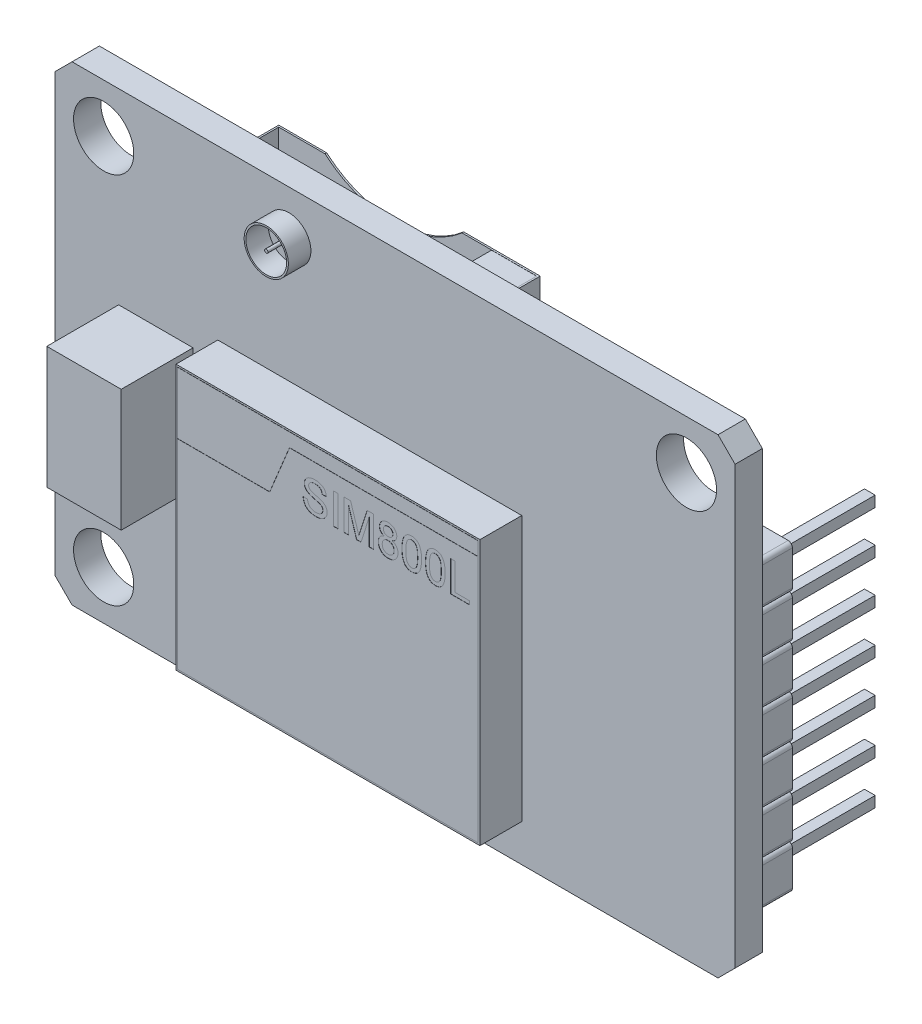
SolidWorks part; units mm, degrees
material "S235 (E24)"
ref_plane "Plan1" through (0, 0, 0) normal (0, 0, 1) x (1, 0, 0)
ref_plane "Plan2" through (0, 0, 0) normal (0, 1, 0) x (1, 0, 0)
ref_plane "Plan3" through (0, 0, 0) normal (1, 0, 0) x (0, 0, -1)
sketch "Esquisse1" plane through (0, 0, 0) normal (0, 0, 1) x (1, 0, 0)
  line L0 (17.075, 10.935) -> (-17.075, 10.935) construction
  line L1 (-19.925, 13.785) -> (19.925, 13.785)
  line L2 (-19.925, 13.785) -> (-19.925, -13.785)
  line L3 (-19.925, -13.785) -> (19.925, -13.785)
  line L4 (19.925, 13.785) -> (19.925, -13.785)
  line L5 (-19.925, 13.785) -> (19.925, -13.785) construction
  line L6 (-19.925, -13.785) -> (19.925, 13.785) construction
  line L7 (-17.075, 10.935) -> (-17.075, -10.935) construction
  line L8 (-17.075, -10.935) -> (17.075, -10.935) construction
  line L9 (17.075, -10.935) -> (17.075, 10.935) construction
  line L10 (0, 0) -> (-17.075, 0) construction
  line L11 (0, 10.935) -> (0, 0) construction
  circle A0 centre (17.075, 10.935) radius 1.765
  circle A1 centre (-17.075, 10.935) radius 1.765
  circle A2 centre (-17.075, -10.935) radius 1.765
  point P0 (0, 0)
  dimension "D3" = 3.53
  dimension "D1" = 39.85
  dimension "D2" = 27.57
  dimension "D4" = 2.85
  dimension "D5" = 2.85
extrude "Boss.-Extru.1" add sketch "Esquisse1" along normal blind 1.6
chamfer "Chanfrein1" distance 1 angle 45 4 edges at (19.925, -13.785, 0.8) (-19.925, -13.785, 0.8) (-19.925, 13.785, 0.8) (19.925, 13.785, 0.8)
sketch "Esquisse2" plane through (0, 0, 1.6) normal (0, 0, 1) x (1, 0, 0)
  line L0 (-18.925, -13.785) -> (18.925, -13.785) construction
  line L1 (-10.385, 3.935) -> (7.425, 3.935)
  line L2 (-10.385, 3.935) -> (-10.385, -11.595)
  line L3 (-10.385, -11.595) -> (7.425, -11.595)
  line L4 (7.425, 3.935) -> (7.425, -11.595)
  line L5 (-10.385, 3.935) -> (7.425, -11.595) construction
  line L6 (-10.385, -11.595) -> (7.425, 3.935) construction
  line L7 (-19.925, 12.785) -> (-19.925, -12.785) construction
  point P0 (-1.48, -3.83)
  dimension "D1" = 17.81
  dimension "D2" = 15.53
  dimension "D3" = 17.72
  dimension "D4" = 27.35
extrude "Boss.-Extru.2" add sketch "Esquisse2" along normal blind 2.46
sketch "Esquisse3" plane through (0, 0, 1.6) normal (0, 0, 1) x (1, 0, 0)
  line L0 (-19.925, 12.785) -> (-19.925, -12.785) construction
  line L1 (-16.195, 2.815) -> (-11.835, 2.815)
  line L2 (-16.195, 2.815) -> (-16.195, -4.335)
  line L3 (-16.195, -4.335) -> (-11.835, -4.335)
  line L4 (-11.835, 2.815) -> (-11.835, -4.335)
  line L5 (-18.925, -13.785) -> (18.925, -13.785) construction
  dimension "D1" = 7.15
  dimension "D2" = 4.36
  dimension "D3" = 8.09
  dimension "D4" = 16.6
extrude "Boss.-Extru.3" add sketch "Esquisse3" along normal blind 4.21
sketch "Esquisse5" plane through (0, 0, 1.6) normal (0, 0, 1) x (1, 0, 0)
  line L0 (18.925, 13.785) -> (-18.925, 13.785) construction
  line L1 (-19.925, 12.785) -> (-19.925, -12.785) construction
  circle A0 centre (-6.225, 11.185) radius 1.295
  dimension "D1" = 2.59
  dimension "D2" = 2.6
  dimension "D3" = 13.7
extrude "Extru.-Mince1" add sketch "Esquisse5" along normal blind 1.32 thin thin type one direction reverse wall 0.1
sketch "Esquisse6" plane through (0, 0, 1.6) normal (0, 0, 1) x (1, 0, 0)
  circle A0 centre (-6.225, 11.185) radius 0.1
  dimension "D1" = 0.2
extrude "Boss.-Extru.4" add sketch "Esquisse6" along normal up to surface (1.32 mm away) up to face at (-4.93, 11.185, 2.92)
sketch "Esquisse7" plane through (0, 0, 0) normal (0, 0, -1) x (-1, 0, 0)
  line L0 (-18.27, 5.46) -> (-18.27, 2.92) construction
  line L1 (-19.535, 6.725) -> (-17.005, 6.725)
  line L2 (-19.535, 6.725) -> (-19.535, 4.195)
  line L3 (-19.535, 4.195) -> (-17.005, 4.195)
  line L4 (-17.005, 6.725) -> (-17.005, 4.195)
  line L5 (-19.535, 6.725) -> (-17.005, 4.195) construction
  line L6 (-19.535, 4.195) -> (-17.005, 6.725) construction
  line L7 (-19.535, 4.185) -> (-17.005, 4.185)
  line L8 (-19.535, 4.185) -> (-19.535, 1.655)
  line L9 (-19.535, 1.655) -> (-17.005, 1.655)
  line L10 (-17.005, 4.185) -> (-17.005, 1.655)
  line L11 (-19.535, 4.185) -> (-17.005, 1.655) construction
  line L12 (-19.535, 1.655) -> (-17.005, 4.185) construction
  line L13 (-19.535, 1.645) -> (-17.005, 1.645)
  line L14 (-19.535, 1.645) -> (-19.535, -0.885)
  line L15 (-19.535, -0.885) -> (-17.005, -0.885)
  line L16 (-17.005, 1.645) -> (-17.005, -0.885)
  line L17 (-19.535, 1.645) -> (-17.005, -0.885) construction
  line L18 (-19.535, -0.885) -> (-17.005, 1.645) construction
  line L19 (-19.535, -0.895) -> (-17.005, -0.895)
  line L20 (-19.535, -0.895) -> (-19.535, -3.425)
  line L21 (-19.535, -3.425) -> (-17.005, -3.425)
  line L22 (-17.005, -0.895) -> (-17.005, -3.425)
  line L23 (-19.535, -0.895) -> (-17.005, -3.425) construction
  line L24 (-19.535, -3.425) -> (-17.005, -0.895) construction
  line L25 (-19.535, -3.435) -> (-17.005, -3.435)
  line L26 (-19.535, -3.435) -> (-19.535, -5.965)
  line L27 (-19.535, -5.965) -> (-17.005, -5.965)
  line L28 (-17.005, -3.435) -> (-17.005, -5.965)
  line L29 (-19.535, -3.435) -> (-17.005, -5.965) construction
  line L30 (-19.535, -5.965) -> (-17.005, -3.435) construction
  line L31 (-19.535, -5.975) -> (-17.005, -5.975)
  line L32 (-19.535, -5.975) -> (-19.535, -8.505)
  line L33 (-19.535, -8.505) -> (-17.005, -8.505)
  line L34 (-17.005, -5.975) -> (-17.005, -8.505)
  line L35 (-19.535, -5.975) -> (-17.005, -8.505) construction
  line L36 (-19.535, -8.505) -> (-17.005, -5.975) construction
  line L37 (-19.535, -8.515) -> (-17.005, -8.515)
  line L38 (-19.535, -8.515) -> (-19.535, -11.045)
  line L39 (-19.535, -11.045) -> (-17.005, -11.045)
  line L40 (-17.005, -8.515) -> (-17.005, -11.045)
  line L41 (-19.535, -8.515) -> (-17.005, -11.045) construction
  line L42 (-19.535, -11.045) -> (-17.005, -8.515) construction
  line L43 (-18.27, 2.92) -> (-18.27, 0.38) construction
  line L44 (-18.27, 0.38) -> (-18.27, -2.16) construction
  line L45 (-18.27, -2.16) -> (-18.27, -4.7) construction
  line L46 (-18.27, -4.7) -> (-18.27, -7.24) construction
  line L47 (-18.27, -7.24) -> (-18.27, -9.78) construction
  line L48 (18.925, -13.785) -> (-18.925, -13.785) construction
  line L49 (-19.925, -12.785) -> (-19.925, 12.785) construction
  point P0 (-18.27, 5.46)
  point P5 (-18.27, 2.92)
  point P10 (-18.27, 0.38)
  point P15 (-18.27, -2.16)
  point P20 (-18.27, -4.7)
  point P25 (-18.27, -7.24)
  point P30 (-18.27, -9.78)
  dimension "D1" = 2.54
  dimension "D2" = 0.01
  dimension "D3" = 20.51
  dimension "D4" = 2.92
extrude "Boss.-Extru.5" add sketch "Esquisse7" along normal blind 2.15
fillet "Congé1" radius 0.25 28 edges at (17.005, 6.725, -1.075) (17.005, 4.195, -1.075) (17.005, 4.185, -1.075) (17.005, 1.655, -1.075) (17.005, 1.645, -1.075) (17.005, -0.885, -1.075) (17.005, -0.895, -1.075) (17.005, -3.425, -1.075) (17.005, -3.435, -1.075) (17.005, -5.965, -1.075) (17.005, -5.975, -1.075) (17.005, -8.505, -1.075) (17.005, -8.515, -1.075) (17.005, -11.045, -1.075) (19.535, -11.045, -1.075) (19.535, -8.515, -1.075) (19.535, -8.505, -1.075) (19.535, -5.975, -1.075) (19.535, -5.965, -1.075) (19.535, -3.435, -1.075) (19.535, -3.425, -1.075) (19.535, -0.895, -1.075) (19.535, -0.885, -1.075) (19.535, 1.645, -1.075) (19.535, 1.655, -1.075) (19.535, 4.185, -1.075) (19.535, 4.195, -1.075) (19.535, 6.725, -1.075)
sketch "Esquisse8" plane through (0, 0, -2.15) normal (0, 0, -1) x (-1, 0, 0)
  line L0 (-19.285, 6.475) -> (-17.255, 4.445) construction
  line L1 (-17.255, 4.445) -> (-17.255, 3.935) construction
  line L2 (-17.255, 3.935) -> (-19.285, 1.905) construction
  line L3 (-19.285, 1.905) -> (-19.285, 1.395) construction
  line L4 (-19.285, 1.395) -> (-17.255, -0.635) construction
  line L5 (-17.255, -0.635) -> (-17.255, -1.145) construction
  line L6 (-17.255, -1.145) -> (-19.285, -3.175) construction
  line L7 (-19.285, -3.175) -> (-19.285, -3.685) construction
  line L8 (-19.285, -3.685) -> (-17.255, -5.715) construction
  line L9 (-17.255, -5.715) -> (-17.255, -6.225) construction
  line L10 (-17.255, -6.225) -> (-19.285, -8.255) construction
  line L11 (-19.285, -8.255) -> (-19.285, -8.765) construction
  line L12 (-19.285, -8.765) -> (-17.255, -10.795) construction
  line L14 (-18.585, 5.775) -> (-17.955, 5.775)
  line L15 (-18.585, 5.775) -> (-18.585, 5.145)
  line L16 (-18.585, 5.145) -> (-17.955, 5.145)
  line L17 (-17.955, 5.775) -> (-17.955, 5.145)
  line L18 (-18.585, 5.775) -> (-17.955, 5.145) construction
  line L19 (-18.585, 5.145) -> (-17.955, 5.775) construction
  line L20 (-18.585, 2.605) -> (-17.955, 2.605)
  line L21 (-18.585, 2.605) -> (-18.585, 3.235)
  line L22 (-18.585, 3.235) -> (-17.955, 3.235)
  line L23 (-17.955, 2.605) -> (-17.955, 3.235)
  line L24 (-18.585, 2.605) -> (-17.955, 3.235) construction
  line L25 (-18.585, 3.235) -> (-17.955, 2.605) construction
  line L26 (-18.585, 0.695) -> (-17.955, 0.695)
  line L27 (-18.585, 0.695) -> (-18.585, 0.065)
  line L28 (-18.585, 0.065) -> (-17.955, 0.065)
  line L29 (-17.955, 0.695) -> (-17.955, 0.065)
  line L30 (-18.585, 0.695) -> (-17.955, 0.065) construction
  line L31 (-18.585, 0.065) -> (-17.955, 0.695) construction
  line L32 (-18.585, -2.475) -> (-17.955, -2.475)
  line L33 (-18.585, -2.475) -> (-18.585, -1.845)
  line L34 (-18.585, -1.845) -> (-17.955, -1.845)
  line L35 (-17.955, -2.475) -> (-17.955, -1.845)
  line L36 (-18.585, -2.475) -> (-17.955, -1.845) construction
  line L37 (-18.585, -1.845) -> (-17.955, -2.475) construction
  line L38 (-18.585, -4.385) -> (-17.955, -4.385)
  line L39 (-18.585, -4.385) -> (-18.585, -5.015)
  line L40 (-18.585, -5.015) -> (-17.955, -5.015)
  line L41 (-17.955, -4.385) -> (-17.955, -5.015)
  line L42 (-18.585, -4.385) -> (-17.955, -5.015) construction
  line L43 (-18.585, -5.015) -> (-17.955, -4.385) construction
  line L44 (-18.585, -7.555) -> (-17.955, -7.555)
  line L45 (-18.585, -7.555) -> (-18.585, -6.925)
  line L46 (-18.585, -6.925) -> (-17.955, -6.925)
  line L47 (-17.955, -7.555) -> (-17.955, -6.925)
  line L48 (-18.585, -7.555) -> (-17.955, -6.925) construction
  line L49 (-18.585, -6.925) -> (-17.955, -7.555) construction
  line L50 (-18.585, -9.465) -> (-17.955, -9.465)
  line L51 (-18.585, -9.465) -> (-18.585, -10.095)
  line L52 (-18.585, -10.095) -> (-17.955, -10.095)
  line L53 (-17.955, -9.465) -> (-17.955, -10.095)
  line L54 (-18.585, -9.465) -> (-17.955, -10.095) construction
  line L55 (-18.585, -10.095) -> (-17.955, -9.465) construction
  point P20 (-18.27, 5.46)
  point P33 (-18.27, 2.92)
  point P38 (-18.27, 0.38)
  point P43 (-18.27, -2.16)
  point P48 (-18.27, -4.7)
  point P53 (-18.27, -7.24)
  point P58 (-18.27, -9.78)
  dimension "D1" = 0.63
extrude "Boss.-Extru.6" add sketch "Esquisse8" along normal blind 5.8
sketch "Esquisse9" plane through (0, 0, 0) normal (0, 0, -1) x (-1, 0, 0)
  line L0 (9.855, 13.585) -> (9.855, -2.265)
  line L1 (9.855, -2.265) -> (-0.985, -2.265)
  line L2 (-0.985, -2.265) -> (-0.985, -3.625)
  line L3 (-0.985, -3.625) -> (-5.465, -3.625)
  line L4 (-5.465, -3.625) -> (-5.465, 13.585)
  line L5 (-5.465, 13.585) -> (-0.985, 13.585)
  line L6 (9.855, 13.585) -> (7.045, 13.585)
  line L7 (-18.925, 13.785) -> (18.925, 13.785) construction
  line L8 (19.925, 12.785) -> (19.925, -12.785) construction
  line L9 (-0.985, 13.585) -> (7.045, 13.585) construction
  line L10 (3.03, 13.585) -> (3.03, 12.085) construction
  arc A0 (-0.985, 13.585) -> (7.045, 13.585) centre (3.03, 18.2084) ccw
  circle A1 centre (5.87, 9.695) radius 0.705
  circle A2 centre (5.87, 2.525) radius 0.705
  circle A3 centre (3.03, 2.525) radius 0.705
  circle A4 centre (0.19, 9.695) radius 0.705
  circle A5 centre (0.19, 2.525) radius 0.705
  circle A6 centre (3.03, 9.695) radius 0.705
  dimension "D11" = 3.89
  dimension "D12" = 1.41
  dimension "D1" = 0.2
  dimension "D2" = 15.85
  dimension "D3" = 15.32
  dimension "D4" = 4.48
  dimension "D5" = 17.21
  dimension "D6" = 25.39
  dimension "D7" = 1.5
  dimension "D8" = 2.81
  dimension "D9" = 7.17
  dimension "D10" = 5.68
extrude "Boss.-Extru.8" add sketch "Esquisse9" along normal blind 1.44
sketch "Esquisse10" plane through (0, 13.585, 0) normal (0, 1, 0) x (1, 0, 0)
  line L0 (0.985, 0) -> (5.465, 0) construction
  line L1 (-9.755, 1.34) -> (2.715, 1.34)
  line L2 (-9.755, 1.34) -> (-9.755, 0)
  line L3 (-9.755, 0) -> (2.715, 0)
  line L4 (2.715, 1.34) -> (2.715, 0)
  line L5 (5.465, 1.44) -> (5.465, 0) construction
  line L7 (-9.855, 1.44) -> (-7.045, 1.44) construction
  line L8 (-9.855, 1.44) -> (-9.855, 0) construction
  point P6 (5.465, 0.72)
  point P10 (-8.45, 1.44)
  dimension "D1" = 0.1
  dimension "D2" = 0.1
  dimension "D3" = 2.75
extrude "Enlèv. mat.-Extru.1" cut sketch "Esquisse10" against normal blind 15.8
sketch "Esquisse11" plane through (0, 13.585, 0) normal (0, 1, 0) x (1, 0, 0)
  line L0 (5.465, 1.44) -> (5.465, 0) construction
  line L1 (2.715, 1.34) -> (5.365, 1.34)
  line L2 (2.715, 1.34) -> (2.715, 0)
  line L3 (2.715, 0) -> (5.365, 0)
  line L4 (5.365, 1.34) -> (5.365, 0)
  dimension "D1" = 0.1
extrude "Enlèv. mat.-Extru.2" cut sketch "Esquisse11" against normal blind 0.01
sketch "Esquisse12" plane through (0, 0, 4.06) normal (0, 0, 1) x (1, 0, 0)
  line L1 (-10.385, 3.935) -> (7.425, 3.935)
  line L2 (-10.385, 3.935) -> (-10.385, -11.595)
  line L3 (-10.385, -11.595) -> (7.425, -11.595)
  line L4 (7.425, 3.935) -> (7.425, -11.595)
extrude "Enlèv. de mat.-Extru.-Mince1" cut sketch "Esquisse12" against normal blind 0.01 thin thin type one direction reverse wall 0.1
sketch "Esquisse13" plane through (0, 0, 4.06) normal (0, 0, 1) x (1, 0, 0)
  line L0 (-10.285, 0.215) -> (-4.885, 0.215)
  line L1 (-10.285, 3.835) -> (-10.285, -11.495) construction
  line L2 (-4.885, 0.215) -> (-3.725, 3.035)
  line L3 (-3.725, 3.035) -> (7.325, 3.035)
  line L4 (7.325, -11.495) -> (7.325, 3.835) construction
  line L5 (7.325, 3.835) -> (-10.285, 3.835) construction
  line L6 (-10.285, 3.835) -> (-10.285, -11.495) construction
  dimension "D1" = 3.62
  dimension "D2" = 0.8
  dimension "D3" = 5.4
  dimension "D4" = 6.56
extrude "Enlèv. de mat.-Extru.-Mince2" cut sketch "Esquisse13" against normal up to surface (0.01 mm away) and the other way through all thin up to face at (-1.48, -3.83, 4.05) thin type one direction wall 0.01
sketch "Esquisse14" plane through (0, 0, 4.06) normal (0, 0, 1) x (1, 0, 0)
  text T0 "SIM800L" font "Arial" height in points 7
extrude "Enlèv. mat.-Extru.3" cut sketch "Esquisse14" against normal blind 0.01
sketch "Esquisse16" plane through (0, 0, 0) normal (0, 0, -1) x (-1, 0, 0)
  text T0 "5VIN" font "Arial" height in points 3
  text T1 "GND" font "Arial" height in points 3
  text T2 "VDD" font "Arial" height in points 3
  text T3 "TXD" font "Arial" height in points 3
  text T4 "RXD" font "Arial" height in points 3
  text T5 "GND" font "Arial" height in points 3
  text T6 "RST" font "Arial" height in points 3
extrude "Enlèv. mat.-Extru.5" cut sketch "Esquisse16" against normal blind 0.01
sketch "Esquisse18" plane through (0, 0, 0) normal (0, 0, -1) x (-1, 0, 0)
  line L0 (-17.255, 6.725) -> (-14.255, 6.725) construction
  line L1 (-13.755, 6.225) -> (-14.255, 6.225) construction
  line L2 (-14.255, 1.655) -> (-17.255, 1.655) construction
  line L3 (-14.255, 6.725) -> (-13.755, 6.225)
  line L4 (-19.285, 1.655) -> (-17.255, 1.655) construction
  line L5 (-13.755, 6.225) -> (-13.755, 2.155)
  line L6 (-13.755, 2.155) -> (-14.255, 1.655)
  line L7 (-13.755, 2.155) -> (-14.255, 2.155) construction
  line L8 (-14.255, 6.225) -> (-14.255, 6.725) construction
  line L9 (-14.255, 6.225) -> (-14.255, 2.155) construction
  line L10 (-14.255, 2.155) -> (-14.255, 1.655) construction
  dimension "D1" = 3
  dimension "D2" = 0.5
sketch "Esquisse19" plane through (0, 0, 0) normal (0, 0, -1) x (-1, 0, 0)
  line L0 (-17.255, -0.895) -> (-14.255, -0.895) construction
  line L1 (-13.755, -8.005) -> (-14.255, -8.005) construction
  line L2 (-14.255, -8.505) -> (-17.255, -8.505) construction
  line L3 (-19.285, -8.505) -> (-17.255, -8.505) construction
  line L4 (-14.255, -0.895) -> (-13.755, -1.395)
  line L5 (-13.755, -1.395) -> (-13.755, -8.005)
  line L6 (-13.755, -8.005) -> (-14.255, -8.505)
  line L7 (-13.755, -1.395) -> (-14.255, -1.395) construction
  line L8 (-14.255, -8.005) -> (-14.255, -8.505) construction
  line L9 (-14.255, -0.895) -> (-14.255, -1.395) construction
  line L10 (-14.255, -1.395) -> (-14.255, -8.005) construction
  dimension "D1" = 0.5
  dimension "D2" = 3
extrude "Enlèv. de mat.-Extru.-Mince3" cut sketch "Esquisse19" against normal blind 0.01 and the other way through all thin thin type one direction wall 0.01
extrude "Enlèv. de mat.-Extru.-Mince8" cut sketch "Esquisse18" against normal blind 0.01 thin thin type one direction wall 0.01
sketch "Esquisse15" plane through (0, 0, 0) normal (0, 0, -1) x (-1, 0, 0)
  line L0 (-13.5167, 6.2491) -> (-13.5167, -2.1532) construction
  line L1 (-13.5167, -2.1532) -> (-13.5167, -6.9904) construction
  text T0 "POWER" font "Arial" height in points 3
  text T1 "UART TTL" font "Arial" height in points 3
extrude "Enlèv. mat.-Extru.4" cut sketch "Esquisse15" against normal blind 0.01
